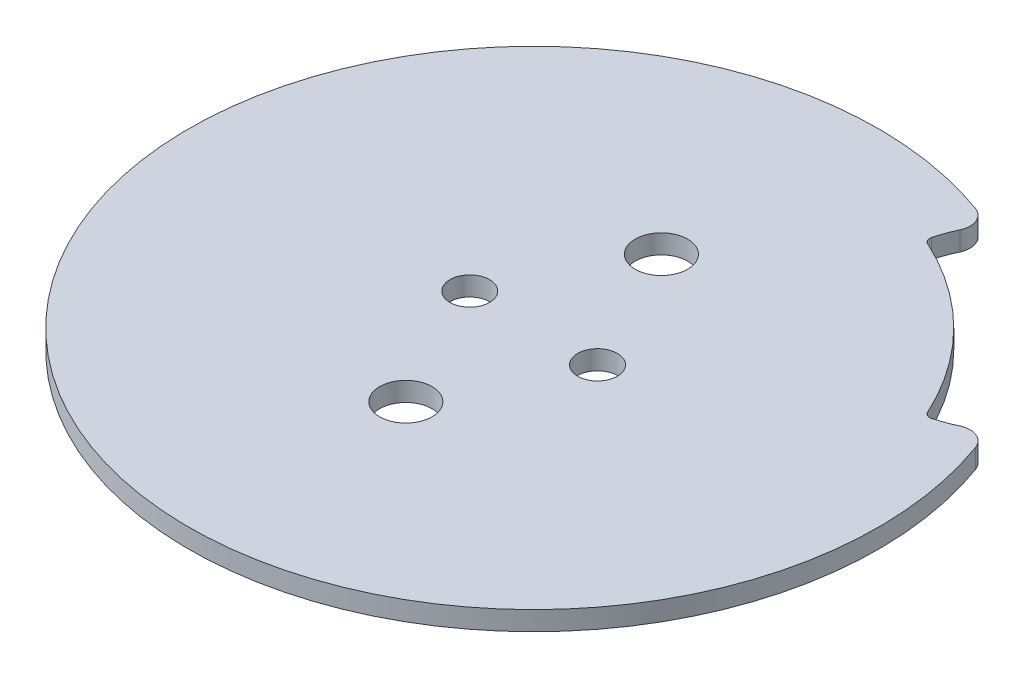
SolidWorks part; units mm, degrees
ref_plane "Front Plane" through (0, 0, 0) normal (0, 0, 1) x (1, 0, 0)
ref_plane "Top Plane" through (0, 0, 0) normal (0, 1, 0) x (1, 0, 0)
ref_plane "Right Plane" through (0, 0, 0) normal (1, 0, 0) x (0, 0, -1)
sketch "Sketch1" plane through (0, 0, 0) normal (0, 1, 0) x (1, 0, 0)
  line L0 (38.1838, 38.1838) -> (0, 0) construction
  line L1 (0, 0) -> (-49.6397, 0) construction
  circle A0 centre (0, 0) radius 54
  circle A1 centre (0, 0) radius 20 construction
  circle A2 centre (0, 20) radius 4.1
  circle A3 centre (0, -20) radius 4.1
  circle A4 centre (-10, 0) radius 3.1
  circle A5 centre (10, 0) radius 3.1
  circle A6 centre (0, 0) radius 10 construction
  circle A7 centre (38.1838, 38.1838) radius 20
  circle A8 centre (0, 0) radius 46.5
  dimension "D1" = 8.2
  dimension "D2" = 40
  dimension "D3" = 108
  dimension "D4" = 20
  dimension "D5" = 6.2
  dimension "D7" = 40
  dimension "D8" = 93
  dimension "D6" = 135
extrude "Boss-Extrude1" add sketch "Sketch1" along normal blind 3 contours A8 A7 A0 | A7 A8 A5 A4 A3 A2 | A7 A8 region at (-43.9213, 0, 28.7106) region at (-1.3404, 0, 1.3404) region at (28.8166, 0, -28.8166)
fillet "Fillet1" radius 3 2 edges at (49.4624, 1.5, -21.6673) (21.6673, 1.5, -49.4624)
fillet "Fillet2" radius 1 2 edges at (42.5855, 1.5, -18.6742) (18.6742, 1.5, -42.5855)
